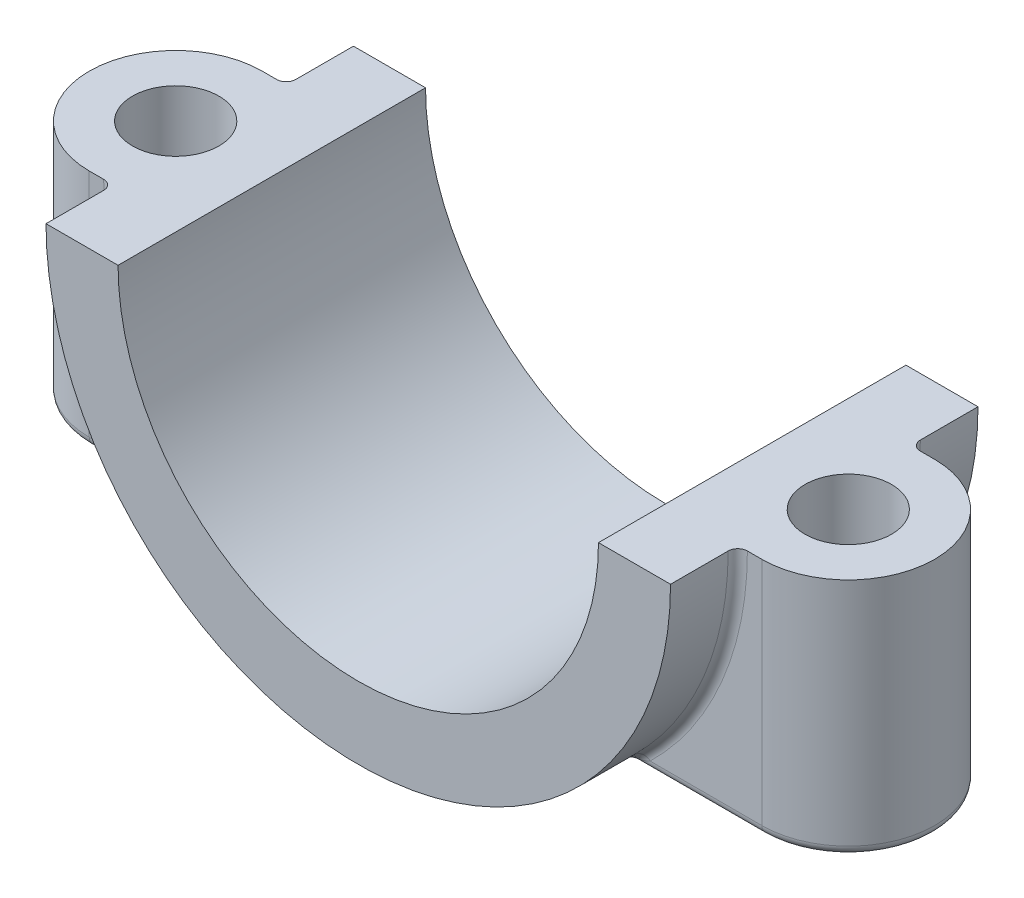
SolidWorks part; units mm, degrees
ref_plane "Piano frontale" through (0, 0, 0) normal (0, 0, 1) x (1, 0, 0)
ref_plane "Piano superiore" through (0, 0, 0) normal (0, 1, 0) x (1, 0, 0)
ref_plane "Piano destro" through (0, 0, 0) normal (1, 0, 0) x (0, 0, -1)
sketch "Schizzo1" plane through (0, 0, 0) normal (0, 1, 0) x (1, 0, 0)
  line L0 (-35, 0) -> (35, 0) construction
  line L1 (-35, 9) -> (35, 9)
  line L2 (-35, -9) -> (35, -9)
  arc A0 (-35, 9) -> (-35, -9) centre (-35, 0) ccw
  arc A1 (35, -9) -> (35, 9) centre (35, 0) ccw
  point P3 (0, 0)
  point P8 (0, 0)
  dimension "D2" = 9
  dimension "D1" = 70
extrude "Estrusione-Estrusione1" add sketch "Schizzo1" along normal blind 25
sketch "Schizzo2" plane through (0, 0, 0) normal (0, 0, 1) x (1, 0, 0)
  line L0 (-35, 25) -> (35, 25) construction
  line L1 (-32.5, 25) -> (32.5, 25)
  arc A0 (-32.5, 25) -> (32.5, 25) centre (0, 25) ccw
  dimension "D1" = 65
extrude "Estrusione-Estrusione2" add sketch "Schizzo2" along normal mid plane 32
sketch "Schizzo3" plane through (0, 0, 0) normal (0, 0, 1) x (1, 0, 0)
  line L0 (32.5, 25) -> (-32.5, 25) construction
  circle A0 centre (0, 25) radius 25
  dimension "D1" = 50
extrude "Taglio-Estrusione1" cut sketch "Schizzo3" against normal mid plane 32
sketch "Schizzo4" plane through (0, 25, 0) normal (0, 1, 0) x (1, 0, 0)
  circle A0 centre (35, 0) radius 4.5
  circle A1 centre (-35, 0) radius 4.5
  dimension "D1" = 9
extrude "Taglio-Estrusione2" cut sketch "Schizzo4" against normal through all both and the other way through all
fillet "Raccordo1" radius 1 14 edges at (-29.4208, 11.1917, 9) (-29.4208, 11.1917, -9) (29.4208, 11.1917, -9) (29.4208, 11.1917, 9) (27.8833, 0, 9) (44, 0, 0) (27.8833, 0, -9) (20.7666, 0, 0) (35, 0, 4.5) (-27.8833, 0, -9) (-44, 0, 0) (-27.8833, 0, 9) (-20.7666, 0, 0) (-35, 0, 4.5)
